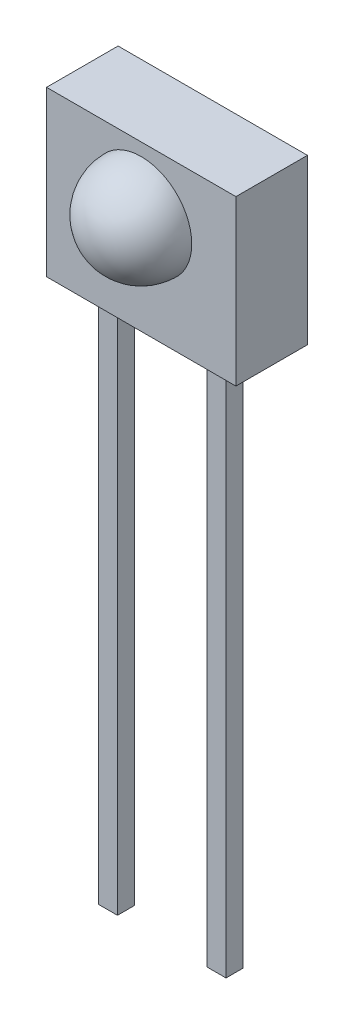
SolidWorks part; units mm, degrees
ref_plane "Front Plane" through (0, 0, 0) normal (0, 0, 1) x (1, 0, 0)
ref_plane "Top Plane" through (0, 0, 0) normal (0, 1, 0) x (1, 0, 0)
ref_plane "Right Plane" through (0, 0, 0) normal (1, 0, 0) x (0, 0, -1)
sketch "Sketch1" plane through (0, 0, 0) normal (0, 0, 1) x (1, 0, 0)
  line L0 (-2.25, -1.95) -> (2.25, -1.95)
  line L1 (-2.25, -1.95) -> (-2.25, 1.95)
  line L2 (2.25, -1.95) -> (2.25, 1.95)
  line L3 (-2.25, 1.95) -> (2.25, 1.95)
  line L4 (-2.25, -1.95) -> (2.25, 1.95) construction
  line L5 (2.25, -1.95) -> (-2.25, 1.95) construction
  point P1 (0, 0)
  dimension "D1" = 3.9
  dimension "D2" = 4.5
extrude "Boss-Extrude1" add sketch "Sketch1" against normal blind 1.7
sketch "Sketch2" plane through (0, 0, 0) normal (0, 0, 1) x (1, 0, 0)
  line L0 (2.25, 1.95) -> (-2.25, 1.95) construction
  circle A0 centre (0, 0.45) radius 1.2
  dimension "D2" = 2.4
  dimension "D1" = 1.5
extrude "Boss-Extrude2" add sketch "Sketch2" along normal blind 1.2
fillet "Fillet1" radius 1.2 1 edges at (1.2, 0.45, 1.2)
sketch "Sketch3" plane through (0, -1.95, 0) normal (0, -1, 0) x (1, 0, 0)
  line L0 (1.065, -0.5) -> (1.515, -0.5)
  line L1 (1.065, -0.5) -> (1.065, -0.9)
  line L2 (1.515, -0.5) -> (1.515, -0.9)
  line L3 (1.065, -0.9) -> (1.515, -0.9)
  line L4 (1.065, -0.5) -> (1.515, -0.9) construction
  line L5 (1.515, -0.5) -> (1.065, -0.9) construction
  point P1 (1.29, -0.7)
  dimension "D1" = 0.45
  dimension "D2" = 0.4
extrude "Boss-Extrude3" add sketch "Sketch3" along normal blind 12.8
mirror "Mirror1" about plane through (0, 0, 0) normal (1, 0, 0) of "Boss-Extrude3"
sketch "Sketch6" plane through (0, 1.95, 0) normal (0, 1, 0) x (1, 0, 0)
  line L0 (0, 0) -> (0, -3.5794) construction
  line L1 (2.25, 0) -> (-2.25, 0) construction
  line L2 (0, 0) -> (-90.6308, -42.2618)
  line L3 (0, 0) -> (90.6308, -42.2618)
  dimension "D1" = 65
  dimension "D2" = 65
  dimension "D3" = 100
  dimension "D4" = 100
